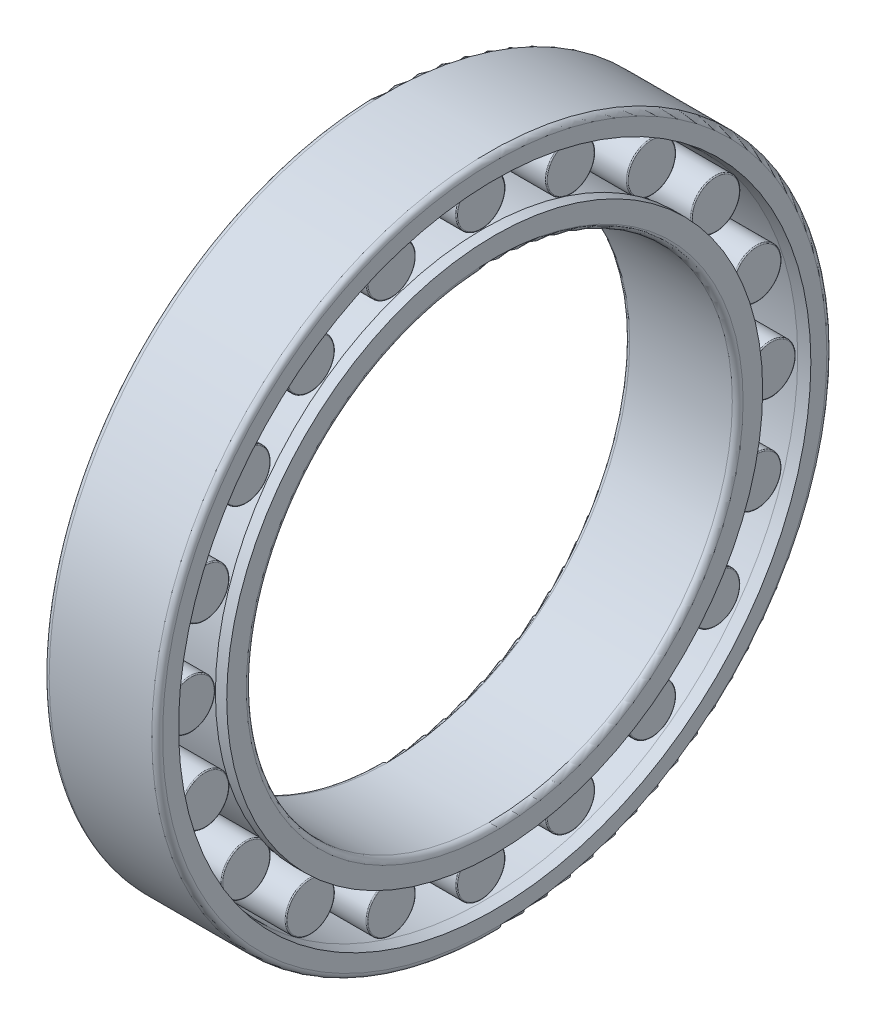
SolidWorks part; units mm, degrees
note: '?' marks a value the reader was unsure of.
ref_plane "Plane1" through (0, 0, 0) normal (0, 0, 1) x (1, 0, 0)
ref_plane "Plane2" through (0, 0, 0) normal (0, 1, 0) x (1, 0, 0)
ref_plane "Plane3" through (0, 0, 0) normal (1, 0, 0) x (0, 0, -1)
sketch "Clipboard" plane through (0, 0, 0) normal (0, 0, 1) x (1, 0, 0)
  line L0 (-10, 0) -> (10, 0) construction
  line L1 (0, 0) -> (185.2698, -67.4327)
  line L2 (0, 0) -> (101.017, 36.7672)
  line L3 (0, 0) -> (218.798, -79.636)
  line L4 (0, 0) -> (-22.3471, -0.7804)
  dimension "Race_OD" = 232.84
  dimension "Race_ID" = 197.16
sketch "OutRacSke" plane through (0, 0, 0) normal (0, 0, 1) x (1, 0, 0)
  line L0 (16.8, 116.42) -> (21, 117.0867)
  line L1 (-21, 117.0867) -> (-21, 123)
  line L2 (-19, 125) -> (19, 125)
  line L3 (21, 123) -> (21, 117.0867)
  line L4 (-16.8, 116.42) -> (-21, 117.0867)
  line L6 (16.8, 116.42) -> (-16.8, 116.42)
  line L8 (-90, 0) -> (90, 0) construction
  arc A0 (-21, 123) -> (-19, 125) centre (-19, 123) cw
  arc A1 (19, 125) -> (21, 123) centre (19, 123) cw
  dimension "Race_OD" = 232.84
  dimension "groove_dp" = 0.6667
  dimension "halfCylLen" = 16.8
  dimension "radius" = 2
  dimension "halfWidth" = 21
  dimension "Cyl_Len" = 33.6
revolve "OuterRace" add sketch "OutRacSke" angle 360 about L8
sketch "RolDetSke" plane through (0, 0, 0) normal (0, 0, 1) x (1, 0, 0)
  line L0 (-15.96, 116.1851) -> (-15.96, 107.5)
  line L1 (-15.96, 107.5) -> (15.96, 107.5)
  line L2 (15.96, 107.5) -> (15.96, 116.1851)
  line L3 (15.5981, 116.547) -> (-15.5981, 116.547)
  line L4 (-33.6, 107.5) -> (33.6, 107.5) construction
  arc A0 (15.96, 116.1851) -> (15.5981, 116.547) centre (15.5981, 116.1851) ccw
  arc A1 (-15.5981, 116.547) -> (-15.96, 116.1851) centre (-15.5981, 116.1851) ccw
  dimension "radius" = 0.3619
  dimension "Roller_diameter" = 18.094
  dimension "halfLength" = 15.96
revolve "RollerDetailed" add sketch "RolDetSke" angle 360 about L4
ref_axis "Axis1" through (-50, 0, 0) along (1, 0, 0)?
sketch "RolSimSke" plane through (0, 101.6, 0) normal (0, 0, 1) x (1, 0, 0)
  line L0 (-15.96, 14.5851) -> (-15.96, -2.7851)
  line L1 (25.4, -101.6) -> (-25.4, -101.6) construction
  line L2 (15.96, -2.7851) -> (15.96, 14.5851)
  line L3 (15.5981, 14.947) -> (-15.5981, 14.947)
  line L5 (15.5981, -3.147) -> (-15.5981, -3.147)
  arc A0 (15.96, 14.5851) -> (15.5981, 14.947) centre (15.5981, 14.5851) ccw
  arc A1 (-15.5981, 14.947) -> (-15.96, 14.5851) centre (-15.5981, 14.5851) ccw
  arc A2 (15.96, -2.7851) -> (15.5981, -3.147) centre (15.5981, -2.7851) cw
  arc A3 (-15.5981, -3.147) -> (-15.96, -2.7851) centre (-15.5981, -2.7851) cw
  dimension "radius" = 0.3619
  dimension "D1" = 98.453
  dimension "Roller_diameter" = 18.094
  dimension "halfLength" = 15.96
revolve "RollersSimplified" [suppressed] add sketch "RolSimSke" angle 360 about L1
sketch "InsRacSke" plane through (0, 0, 0) normal (0, 0, 1) x (1, 0, 0)
  line L0 (16.8, 98.58) -> (16.8, 99.2467)
  line L1 (-21, 99.2467) -> (-21, 92)
  line L2 (-19, 90) -> (19, 90)
  line L3 (21, 92) -> (21, 99.2467)
  line L4 (16.8, 99.2467) -> (21, 99.2467)
  line L5 (16.8, 98.58) -> (-16.8, 98.58)
  line L6 (-90, 0) -> (90, 0) construction
  line L8 (-16.8, 98.58) -> (-16.8, 99.2467)
  line L9 (-16.8, 99.2467) -> (-21, 99.2467)
  arc A0 (-21, 92) -> (-19, 90) centre (-19, 92) ccw
  arc A1 (19, 90) -> (21, 92) centre (19, 92) ccw
  dimension "groove_dp" = 0.6667
  dimension "halfCylLen" = 16.8
  dimension "radius" = 2
  dimension "Race_ID" = 197.16
  dimension "Width" = 42
  dimension "halfWidth" = 21
  dimension "Cyl_Len" = 33.6
revolve "InnerRace" add sketch "InsRacSke" angle 360 about L6
pattern_circular "RollersDetailed" count 20 over 360 about axis through (0, 0, 0) along (1, 0, 0) of "RollerDetailed"
sketch "CagSpiSke" plane through (0, 0, 0) normal (0, 0, 1) x (1, 0, 0)
  line L0 (18.9, 105.2383) -> (18.9, 109.7618)
  line L1 (18.9, 109.7618) -> (-18.9, 109.7618)
  line L2 (-18.9, 109.7618) -> (-18.9, 105.2383)
  line L3 (-18.9, 105.2383) -> (18.9, 105.2383)
  line L4 (-90, 0) -> (90, 0) construction
revolve "CageSpine" [suppressed] add sketch "CagSpiSke" angle 360 about L4
equation "\"CLdia@Clipboard\" =  ( \"Race_OD@Clipboard\" + \"Race_ID@Clipboard\" )  / 4"
equation "\"Race_OD@OutRacSke\" = \"Race_OD@Clipboard\""
equation "\"halfCylLen@OutRacSke\" = \"Cyl_Len@OutRacSke\" / 2"
equation "\"groove_dp@OutRacSke\" = \"radius@OutRacSke\" / 3"
equation "\"RolCLRad@RolDetSke\" = \"CLdia@Clipboard\""
equation "\"Roller_diameter@RolDetSke\" =  ( \"Race_OD@Clipboard\" - \"Race_ID@Clipboard\" )  / 2 + .01"
equation "\"Roller_diameter@RolSimSke\" =  ( \"Race_OD@Clipboard\" - \"Race_ID@Clipboard\" )  / 2 + .01"
equation "\"radius@RolDetSke\" = \"Roller_diameter@RolDetSke\" / 50"
equation "\"Length@RolDetSke\" = \"Cyl_Len@OutRacSke\" * .95"
equation "\"halfLength@RolDetSke\" = \"Length@RolDetSke\" / 2"
equation "\"thickness@CagSpiSke\"  = \"Roller_diameter@RolDetSke\" * .25"
equation "\"Cag_IR@CagSpiSke\" =  \"RolCLRad@RolDetSke\" * 2 - \"thickness@CagSpiSke\""
equation "\"Rol_Length@RolSimSke\" = \"Cyl_Len@InsRacSke\" * .95"
equation "\"halfLength@RolSimSke\" = \"Rol_Length@RolSimSke\" / 2"
equation "\"radius@RolSimSke\" = \"radius@RolDetSke\""
equation "\"D1@RolSimSke\" = \"CLdia@Clipboard\" -  ( \"Roller_diameter@RolSimSke\" / 2 ) "
equation "\"Max_count@Clipboard\" = int( 3.14159265 / atn(( \"Roller_diameter@RolDetSke\" / 2) / sqr( \"RolCLRad@RolDetSke\"  *  \"RolCLRad@RolDetSke\" - ( \"Roller_diameter@RolDetSke\" / 2) *  ( \"Roller_diameter@RolDetSke\" / 2))))"
equation "\"Max_count@Clipboard\" = ((sgn( \"Max_count@Clipboard\" - \"Count@Clipboard\" )-1)*( \"Max_count@Clipboard\" - \"Count@Clipboard\" ))/-2+ \"Count@Clipboard\""
equation "\"Count@RollersDetailed\" = int( \"Show_count@Clipboard\" ) "
equation "\"Count@RollersDetailed\" = ((sgn( \"Count@RollersDetailed\" - \"Max_count@Clipboard\" )-1)*( \"Count@RollersDetailed\" - \"Max_count@Clipboard\" ))/-2+ \"Max_count@Clipboard\""
equation "\"Count@RollersDetailed\" = ((sgn( \"Count@RollersDetailed\" - \"Min_count@Clipboard\" )+1)*( \"Count@RollersDetailed\" - \"Min_count@Clipboard\"))/2 +\"Min_count@Clipboard\""
equation "\"Angle@RollersDetailed\" = 360.0 / \"Max_count@Clipboard\""
equation "\"radius@InsRacSke\" = \"radius@OutRacSke\""
equation "\"Width@InsRacSke\" = \"Width@OutRacSke\""
equation "\"halfWidth@OutRacSke\" = \"Width@OutRacSke\" / 2"
equation "\"halfWidth@InsRacSke\" = \"Width@InsRacSke\" / 2"
equation "\"Race_ID@InsRacSke\" = \"Race_ID@Clipboard\""
equation "\"Cyl_Len@InsRacSke\" = \"Cyl_Len@OutRacSke\""
equation "\"halfCylLen@InsRacSke\" = \"Cyl_Len@InsRacSke\" / 2"
equation "\"Angle@CageSpine\" =  \"Angle@RollersDetailed\" * ( \"Count@RollersDetailed\" -1 + int( \"Count@RollersDetailed\" / \"Max_count@Clipboard\" ) )  + 0.001 -  int( \"Count@RollersDetailed\" / \"Max_count@Clipboard\" ) * 0.001"
equation "\"Angle@CageSpine\" =  \"Angle@CageSpine\" * int( \"Min_count@Clipboard\" / 2) + int(1 / \"Min_count@Clipboard\")  * 0.001"
equation "\"width@CagSpiSke\" =   ( \"Width@InsRacSke\" + \"Cyl_Len@InsRacSke\" )  / 2"
equation "\"halfwidth@CagSpiSke\" = \"width@CagSpiSke\" / 2"
